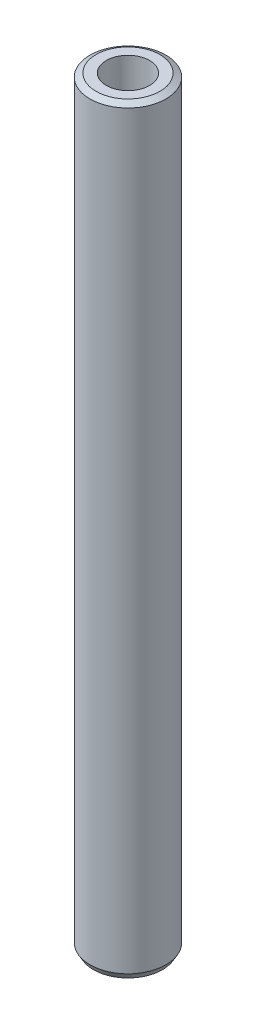
SolidWorks part; units mm, degrees
ref_plane "Front Plane" through (0, 0, 0) normal (0, 0, 1) x (1, 0, 0)
ref_plane "Top Plane" through (0, 0, 0) normal (0, 1, 0) x (1, 0, 0)
ref_plane "Right Plane" through (0, 0, 0) normal (1, 0, 0) x (0, 0, -1)
sketch "Sketch1" plane through (0, 0, 0) normal (0, 1, 0) x (1, 0, 0)
  circle A0 centre (0, 0) radius 20
  dimension "SHAFT_OD" = 40
extrude "Boss-Extrude1" add sketch "Sketch1" along normal blind 399.7636
sketch "Sketch2" plane through (0, 0, 0) normal (0, 1, 0) x (1, 0, 0)
  circle A0 centre (0, 0) radius 11.4138
  dimension "BORE_D" = 22.8275
extrude "Cut-Extrude1" cut sketch "Sketch2" along normal through all
chamfer "Chamfer1" distance 1.8504 angle 60 2 edges at (0, 399.7636, 20) (0, 0, 20) first distance on face at (0, 399.7636, 20) first distance on face at (0, 0, 11.4138)
